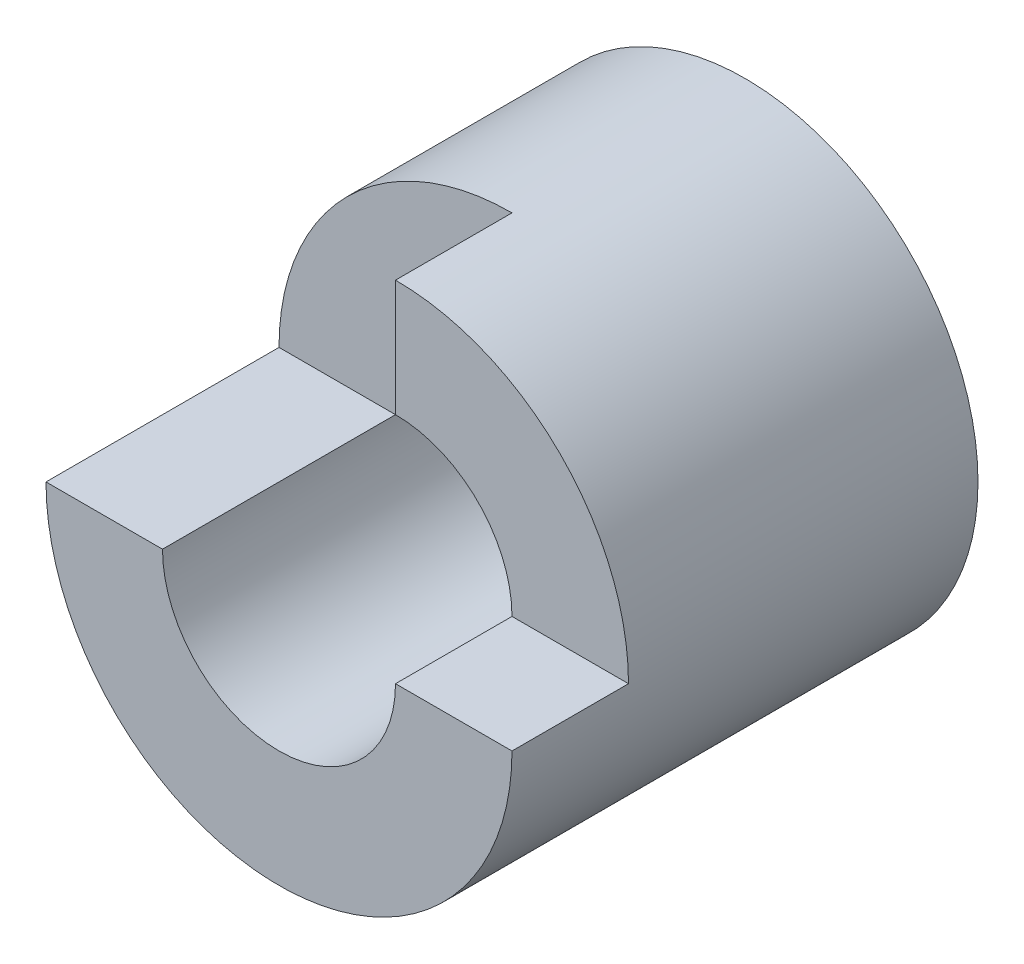
SolidWorks part; units mm, degrees
ref_plane "Front Plane" through (0, 0, 0) normal (0, 0, 1) x (1, 0, 0)
ref_plane "Top Plane" through (0, 0, 0) normal (0, 1, 0) x (1, 0, 0)
ref_plane "Right Plane" through (0, 0, 0) normal (1, 0, 0) x (0, 0, -1)
sketch "Sketch1" plane through (0, 0, 0) normal (0, 0, 1) x (1, 0, 0)
  circle A0 centre (0, 0) radius 20
  dimension "D1" = 40
extrude "Boss-Extrude1" add sketch "Sketch1" along normal blind 40
sketch "Sketch2" plane through (0, 0, 0) normal (1, 0, 0) x (0, 0, -1)
  line L1 (-40, 20) -> (-30, 20)
  line L2 (-40, 20) -> (-40, 0)
  line L3 (-40, 0) -> (-30, 0)
  line L4 (-30, 20) -> (-30, 0)
  dimension "D1" = 10
  dimension "D2" = 20
extrude "Cut-Extrude1" cut sketch "Sketch2" against normal blind 40 and the other way blind 40
sketch "Sketch3" plane through (0, 0, 30) normal (0, 0, 1) x (1, 0, 0)
  circle A0 centre (0, 0) radius 10
  dimension "D1" = 20
extrude "Cut-Extrude2" cut sketch "Sketch3" against normal blind 40 and the other way blind 40
sketch "Sketch4" plane through (0, 0, 30) normal (0, 0, 1) x (1, 0, 0)
  line L0 (-10, 0) -> (-20, 0) construction
  line L1 (-20, 0) -> (-10, 0)
  line L2 (0, 10) -> (0, 20)
  arc A0 (0, 10) -> (-10, 0) centre (0, 0) ccw
  arc A1 (10, 0) -> (-10, 0) centre (0, 0) ccw construction
  arc A2 (0, 20) -> (-20, 0) centre (0, 0) ccw
  arc A3 (20, 0) -> (-20, 0) centre (0, 0) ccw construction
extrude "Cut-Extrude3" cut sketch "Sketch4" against normal blind 10
